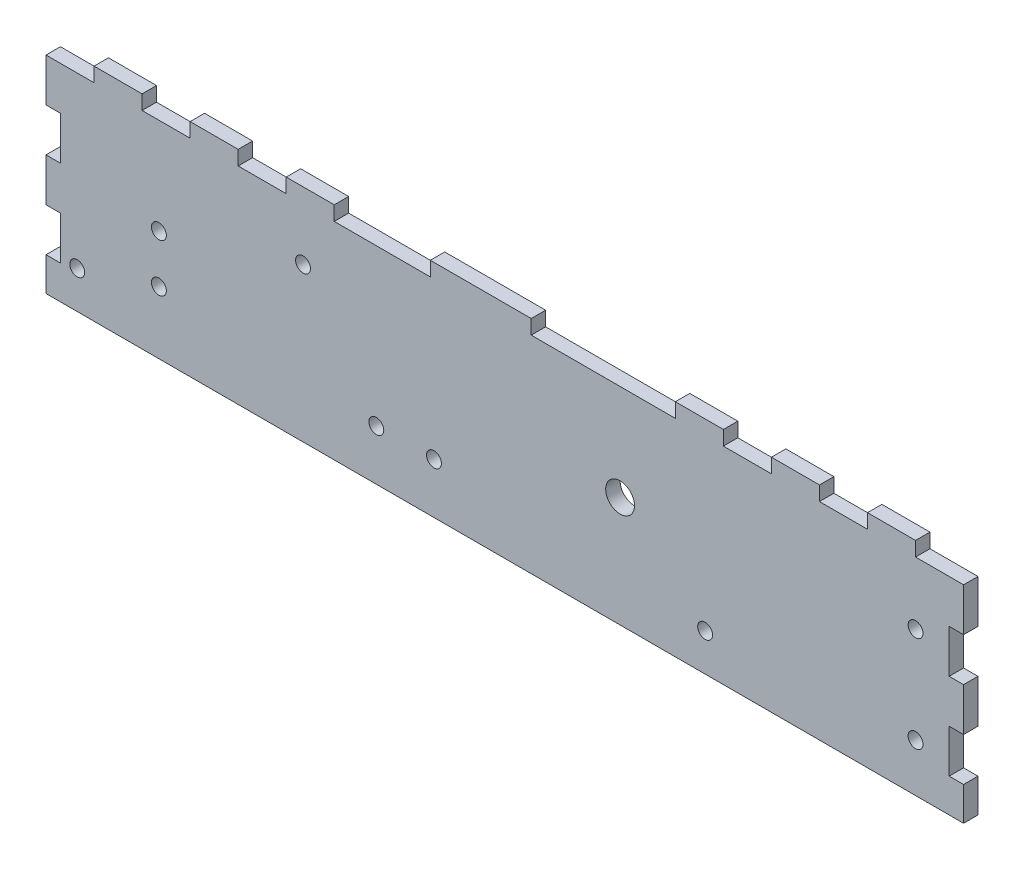
SolidWorks part; units mm, degrees
ref_plane "Front Plane" through (0, 0, 0) normal (0, 0, 1) x (1, 0, 0)
ref_plane "Top Plane" through (0, 0, 0) normal (0, 1, 0) x (1, 0, 0)
ref_plane "Right Plane" through (0, 0, 0) normal (1, 0, 0) x (0, 0, -1)
sketch "Sketch1" plane through (0, 0, 0) normal (0, 0, 1) x (1, 0, 0)
  line L4 (0, 0) -> (191, 0)
  line L5 (191, 0) -> (191, 46)
  line L6 (191, 46) -> (0, 46)
  line L7 (0, 46) -> (0, 0)
  line L8 (0, 0) -> (191, 0)
  line L9 (191, 0) -> (191, 46)
  line L10 (191, 46) -> (0, 46)
  line L11 (0, 46) -> (0, 0)
  circle A0 centre (181, 30) radius 1.55 construction
  circle A1 centre (181, 10) radius 1.55 construction
  circle A2 centre (181, 30) radius 1.55
  circle A3 centre (181, 10) radius 1.55
  dimension "D1" = 0
extrude "Boss-Extrude1" add sketch "Sketch1" along normal blind 3
sketch "Sketch3" plane through (0, 0, 3) normal (0, 0, 1) x (1, 0, 0)
  line L0 (119.5, 46) -> (119.5, 0) construction
  line L1 (119.5, 46) -> (119.5, 0)
  point P2 (119.5, 23)
ref_point "MountPoint-Sus"
sketch "Sketch4" plane through (0, 0, 0) normal (0, 0, -1) x (-1, 0, 0)
  line L0 (-10, 43) -> (-10, 46) construction
  line L1 (-10, 46) -> (0, 46) construction
  line L2 (0, 46) -> (0, 43) construction
  line L3 (0, 43) -> (-10, 43) construction
  line L4 (-30, 43) -> (-30, 46) construction
  line L5 (-30, 46) -> (-20, 46) construction
  line L6 (-20, 46) -> (-20, 43) construction
  line L7 (-20, 43) -> (-30, 43) construction
  line L8 (-50, 43) -> (-50, 46) construction
  line L9 (-50, 46) -> (-40, 46) construction
  line L10 (-40, 46) -> (-40, 43) construction
  line L11 (-40, 43) -> (-50, 43) construction
  line L12 (-60, 43) -> (-80, 43) construction
  line L13 (-80, 43) -> (-80, 46) construction
  line L14 (-80, 46) -> (-60, 46) construction
  line L15 (-60, 46) -> (-60, 43) construction
  line L16 (-131, 43) -> (-131, 46) construction
  line L17 (-131, 46) -> (-101, 46) construction
  line L18 (-101, 46) -> (-101, 43) construction
  line L19 (-101, 43) -> (-131, 43) construction
  line L20 (-151, 43) -> (-151, 46) construction
  line L21 (-151, 46) -> (-141, 46) construction
  line L22 (-141, 46) -> (-141, 43) construction
  line L23 (-141, 43) -> (-151, 43) construction
  line L24 (-171, 43) -> (-171, 46) construction
  line L25 (-171, 46) -> (-161, 46) construction
  line L26 (-161, 46) -> (-161, 43) construction
  line L27 (-161, 43) -> (-171, 43) construction
  line L28 (-191, 46) -> (-181, 46) construction
  line L29 (-181, 46) -> (-181, 43) construction
  line L30 (-181, 43) -> (-191, 43) construction
  line L31 (-191, 43) -> (-191, 46) construction
  line L32 (-10, 43) -> (-10, 46)
  line L33 (-10, 46) -> (0, 46)
  line L34 (0, 46) -> (0, 43)
  line L35 (0, 43) -> (-10, 43)
  line L36 (-30, 43) -> (-30, 46)
  line L37 (-30, 46) -> (-20, 46)
  line L38 (-20, 46) -> (-20, 43)
  line L39 (-20, 43) -> (-30, 43)
  line L40 (-50, 43) -> (-50, 46)
  line L41 (-50, 46) -> (-40, 46)
  line L42 (-40, 46) -> (-40, 43)
  line L43 (-40, 43) -> (-50, 43)
  line L44 (-60, 43) -> (-80, 43)
  line L45 (-80, 43) -> (-80, 46)
  line L46 (-80, 46) -> (-60, 46)
  line L47 (-60, 46) -> (-60, 43)
  line L48 (-131, 43) -> (-131, 46)
  line L49 (-131, 46) -> (-101, 46)
  line L50 (-101, 46) -> (-101, 43)
  line L51 (-101, 43) -> (-131, 43)
  line L52 (-151, 43) -> (-151, 46)
  line L53 (-151, 46) -> (-141, 46)
  line L54 (-141, 46) -> (-141, 43)
  line L55 (-141, 43) -> (-151, 43)
  line L56 (-171, 43) -> (-171, 46)
  line L57 (-171, 46) -> (-161, 46)
  line L58 (-161, 46) -> (-161, 43)
  line L59 (-161, 43) -> (-171, 43)
  line L60 (-191, 46) -> (-181, 46)
  line L61 (-181, 46) -> (-181, 43)
  line L62 (-181, 43) -> (-191, 43)
  line L63 (-191, 43) -> (-191, 46)
extrude "Cut-Extrude1" cut sketch "Sketch4" against normal up to next
sketch "Sketch5" plane through (0, 0, 0) normal (0, 0, -1) x (-1, 0, 0)
  line L4 (0, 34) -> (-3, 34)
  line L5 (0, 25) -> (0, 34)
  line L6 (-3, 25) -> (0, 25)
  line L7 (-3, 34) -> (-3, 25)
  line L8 (0, 34) -> (-3, 34)
  line L9 (0, 25) -> (0, 34)
  line L10 (-3, 25) -> (0, 25)
  line L11 (-3, 34) -> (-3, 25)
  line L12 (-3, 7) -> (0, 7)
  line L13 (0, 7) -> (0, 16)
  line L14 (0, 16) -> (-3, 16)
  line L15 (-3, 16) -> (-3, 7)
  line L16 (-3, 7) -> (0, 7)
  line L17 (0, 7) -> (0, 16)
  line L18 (0, 16) -> (-3, 16)
  line L19 (-3, 16) -> (-3, 7)
  dimension "D1" = 0
  dimension "D2" = 0
extrude "Cut-Extrude2" cut sketch "Sketch5" against normal up to next
sketch "Sketch6" plane through (0, 0, 0) normal (0, 0, -1) x (-1, 0, 0)
  line L0 (-188, 25) -> (-188, 34) construction
  line L1 (-188, 34) -> (-191, 34) construction
  line L2 (-191, 25) -> (-188, 25) construction
  line L3 (-188, 16) -> (-191, 16) construction
  line L4 (-188, 7) -> (-188, 16) construction
  line L5 (-191, 7) -> (-188, 7) construction
  line L6 (-188, 25) -> (-188, 34)
  line L7 (-188, 34) -> (-191, 34)
  line L8 (-191, 25) -> (-188, 25)
  line L9 (-188, 16) -> (-191, 16)
  line L10 (-188, 7) -> (-188, 16)
  line L11 (-191, 7) -> (-188, 7)
  line L40 (-3, 7) -> (-3, 16)
  line L41 (-3, 16) -> (0, 16)
  line L42 (0, 16) -> (0, 25)
  line L43 (0, 25) -> (-3, 25)
  line L44 (-3, 25) -> (-3, 34)
  line L45 (-3, 34) -> (0, 34)
  line L46 (0, 34) -> (0, 43)
  line L47 (0, 43) -> (-10, 43)
  line L48 (-10, 43) -> (-10, 46)
  line L49 (-10, 46) -> (-20, 46)
  line L50 (-20, 46) -> (-20, 43)
  line L51 (-20, 43) -> (-30, 43)
  line L52 (-30, 43) -> (-30, 46)
  line L53 (-30, 46) -> (-40, 46)
  line L54 (-40, 46) -> (-40, 43)
  line L55 (-40, 43) -> (-50, 43)
  line L56 (-50, 43) -> (-50, 46)
  line L57 (-50, 46) -> (-60, 46)
  line L58 (-60, 46) -> (-60, 43)
  line L59 (-60, 43) -> (-80, 43)
  line L60 (-80, 43) -> (-80, 46)
  line L61 (-80, 46) -> (-101, 46)
  line L62 (-101, 46) -> (-101, 43)
  line L63 (-101, 43) -> (-131, 43)
  line L64 (-131, 43) -> (-131, 46)
  line L65 (-131, 46) -> (-141, 46)
  line L66 (-141, 46) -> (-141, 43)
  line L67 (-141, 43) -> (-151, 43)
  line L68 (-151, 43) -> (-151, 46)
  line L69 (-151, 46) -> (-161, 46)
  line L70 (-161, 46) -> (-161, 43)
  line L71 (-161, 43) -> (-171, 43)
  line L72 (-171, 43) -> (-171, 46)
  line L73 (-171, 46) -> (-181, 46)
  line L74 (-181, 46) -> (-181, 43)
  line L75 (-181, 43) -> (-191, 43)
  line L76 (-191, 43) -> (-191, 0)
  line L77 (-191, 0) -> (0, 0)
  line L78 (0, 0) -> (0, 7)
  line L79 (0, 7) -> (-3, 7)
  line L80 (-3, 7) -> (-3, 16)
  line L81 (-3, 16) -> (0, 16)
  line L82 (0, 16) -> (0, 25)
  line L83 (0, 25) -> (-3, 25)
  line L84 (-3, 25) -> (-3, 34)
  line L85 (-3, 34) -> (0, 34)
  line L86 (0, 34) -> (0, 43)
  line L87 (0, 43) -> (-10, 43)
  line L88 (-10, 43) -> (-10, 46)
  line L89 (-10, 46) -> (-20, 46)
  line L90 (-20, 46) -> (-20, 43)
  line L91 (-20, 43) -> (-30, 43)
  line L92 (-30, 43) -> (-30, 46)
  line L93 (-30, 46) -> (-40, 46)
  line L94 (-40, 46) -> (-40, 43)
  line L95 (-40, 43) -> (-50, 43)
  line L96 (-50, 43) -> (-50, 46)
  line L97 (-50, 46) -> (-60, 46)
  line L98 (-60, 46) -> (-60, 43)
  line L99 (-60, 43) -> (-80, 43)
  line L100 (-80, 43) -> (-80, 46)
  line L101 (-80, 46) -> (-101, 46)
  line L102 (-101, 46) -> (-101, 43)
  line L103 (-101, 43) -> (-131, 43)
  line L104 (-131, 43) -> (-131, 46)
  line L105 (-131, 46) -> (-141, 46)
  line L106 (-141, 46) -> (-141, 43)
  line L107 (-141, 43) -> (-151, 43)
  line L108 (-151, 43) -> (-151, 46)
  line L109 (-151, 46) -> (-161, 46)
  line L110 (-161, 46) -> (-161, 43)
  line L111 (-161, 43) -> (-171, 43)
  line L112 (-171, 43) -> (-171, 46)
  line L113 (-171, 46) -> (-181, 46)
  line L114 (-181, 46) -> (-181, 43)
  line L115 (-181, 43) -> (-191, 43)
  line L116 (-191, 43) -> (-191, 0)
  line L117 (-191, 0) -> (0, 0)
  line L118 (0, 0) -> (0, 7)
  line L119 (0, 7) -> (-3, 7)
  line M78 (-191, 43) -> (-191, 0)
  dimension "D1" = 0
extrude "Cut-Extrude3" cut sketch "Sketch6" against normal up to next contours L8 L6 L7 M78 | L11 L10 L9 M78 region at (189.5, 29.5, 0) region at (189.5, 11.5, 0)
sketch "Sketch7" plane through (0, 0, 3) normal (0, 0, 1) x (1, 0, 0)
  circle A0 centre (119.5, 23) radius 3
  point P0 (119.5, 23)
  dimension "D1" = 6
extrude "Cut-Extrude4" cut sketch "Sketch7" against normal up to next
sketch "Sketch8" plane through (0, 0, 3) normal (0, 0, 1) x (1, 0, 0)
  circle A0 centre (23.5, 13) radius 1.55 construction
  circle A1 centre (23.5, 23) radius 1.55 construction
  circle A2 centre (53.5, 32) radius 1.55 construction
  circle A3 centre (68.7574, 10.5) radius 1.55 construction
  circle A4 centre (80.7574, 10.5) radius 1.55 construction
  circle A5 centre (23.5, 13) radius 1.55
  circle A6 centre (23.5, 23) radius 1.55
  circle A7 centre (53.5, 32) radius 1.55
  circle A8 centre (68.7574, 10.5) radius 1.55
  circle A9 centre (80.7574, 10.5) radius 1.55
extrude "Cut-Extrude5" cut sketch "Sketch8" against normal up to next
sketch "Sketch9" plane through (0, 0, 0) normal (0, 0, -1) x (-1, 0, 0)
  circle A0 centre (-137.2, 7.8) radius 1.55 construction
  circle A1 centre (-6.5, 7.8) radius 1.55 construction
  circle A2 centre (-137.2, 7.8) radius 1.55
  circle A3 centre (-6.5, 7.8) radius 1.55
extrude "Cut-Extrude6" cut sketch "Sketch9" against normal up to next
